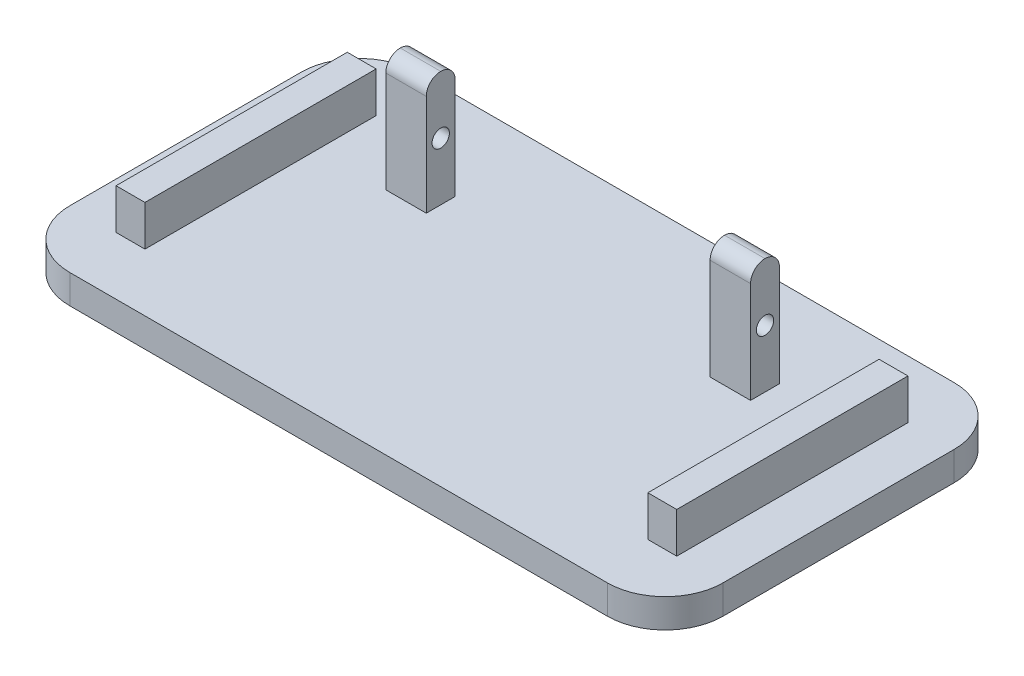
SolidWorks part; units mm, degrees
material "ABS"
ref_plane "Plano frontal" through (0, 0, 0) normal (0, 0, 1) x (1, 0, 0)
ref_plane "Plano superior" through (0, 0, 0) normal (0, 1, 0) x (1, 0, 0)
ref_plane "Plano direito" through (0, 0, 0) normal (1, 0, 0) x (0, 0, -1)
sketch "Esboço1" plane through (0, 0, 0) normal (0, 1, 0) x (1, 0, 0)
  line L1 (-13.2145, 15.5332) -> (79.7855, 15.5332)
  line L2 (-23.2145, 5.5332) -> (-23.2145, -34.4668)
  line L3 (-13.2145, -44.4668) -> (79.7855, -44.4668)
  line L4 (89.7855, 5.5332) -> (89.7855, -34.4668)
  arc A0 (89.7855, 5.5332) -> (79.7855, 15.5332) centre (79.7855, 5.5332) ccw
  arc A1 (89.7855, -34.4668) -> (79.7855, -44.4668) centre (79.7855, -34.4668) cw
  arc A2 (-13.2145, -44.4668) -> (-23.2145, -34.4668) centre (-13.2145, -34.4668) cw
  arc A3 (-23.2145, 5.5332) -> (-13.2145, 15.5332) centre (-13.2145, 5.5332) cw
  point P4 (33.2855, 15.5332)
  point P7 (89.7855, 15.5332)
  point P12 (-23.2145, -44.4668)
  point P15 (-23.2145, 15.5332)
  dimension "D4" = 10
  dimension "D1" = 113
  dimension "D2" = 56.5
  dimension "D3" = 60
extrude "Ressalto-extrusão1" add sketch "Esboço1" along normal blind 5
sketch "Esboço2" plane through (0, 5, 0) normal (0, 1, 0) x (1, 0, 0)
  line L0 (79.7855, 15.5332) -> (-13.2145, 15.5332) construction
  line L1 (-8.2645, -4.7476) -> (-8.2645, 0.2524) construction
  line L2 (64.3755, -4.7476) -> (64.3755, 0.2524) construction
  line L3 (-8.2645, -4.7476) -> (64.3755, -4.7476) construction
  line L4 (-8.2645, 0.2524) -> (64.3755, 0.2524) construction
  line L5 (57.8355, 0.2524) -> (57.8355, -4.7476)
  line L6 (1.7355, 0.2524) -> (8.7355, 0.2524)
  line L7 (1.7355, -4.7476) -> (8.7355, -4.7476)
  line L8 (1.7355, 0.2524) -> (1.7355, -4.7476)
  line L9 (8.7355, 0.2524) -> (8.7355, -4.7476)
  line L10 (64.8355, 0.2524) -> (64.8355, -4.7476)
  line L11 (57.8355, 0.2524) -> (64.8355, 0.2524)
  line L12 (57.8355, -4.7476) -> (64.8355, -4.7476)
  line L13 (89.7855, -34.4668) -> (89.7855, 5.5332) construction
  line L15 (-23.2145, 5.5332) -> (-23.2145, -34.4668) construction
  point P8 (1.7355, -2.2476)
  dimension "D1" = 49.1
  dimension "D2" = 7
  dimension "D3" = 24.95
  dimension "D4" = 24.95
  dimension "D5" = 7
  dimension "D6" = 15.2808
extrude "Ressalto-extrusão2" add sketch "Esboço2" along normal blind 20
sketch "Esboço4" plane through (1.7355, 0, 0) normal (-1, 0, 0) x (0, 0, 1)
  line L0 (-0.2524, 5) -> (4.7476, 5) construction
  line L1 (4.7476, 25) -> (4.7476, 5) construction
  circle A0 centre (2.2476, 15) radius 1.5
  dimension "D1" = 10
  dimension "D2" = 2.5
extrude "Corte-extrusão1" cut sketch "Esboço4" against normal through all
sketch "Esboço5" plane through (0, 5, 0) normal (0, 1, 0) x (1, 0, 0)
  line L0 (79.7855, 15.5332) -> (-13.2145, 15.5332) construction
  line L1 (-15.2145, 5.5332) -> (-10.2145, 5.5332)
  line L2 (-15.2145, 5.5332) -> (-15.2145, -34.4668)
  line L3 (-15.2145, -34.4668) -> (-10.2145, -34.4668)
  line L4 (-10.2145, 5.5332) -> (-10.2145, -34.4668)
  line L5 (-13.2145, -44.4668) -> (79.7855, -44.4668) construction
  line L6 (-23.2145, 5.5332) -> (-23.2145, -34.4668) construction
  line L7 (89.7855, -34.4668) -> (89.7855, 5.5332) construction
  line L8 (76.7855, 5.5332) -> (81.7855, 5.5332)
  line L9 (76.7855, 5.5332) -> (76.7855, -34.4668)
  line L10 (76.7855, -34.4668) -> (81.7855, -34.4668)
  line L11 (81.7855, 5.5332) -> (81.7855, -34.4668)
  dimension "D1" = 10
  dimension "D2" = 10
  dimension "D3" = 8
  dimension "D4" = 40
  dimension "D5" = 10
  dimension "D6" = 8
extrude "Ressalto-extrusão3" add sketch "Esboço5" along normal blind 7
fillet "Filete1" radius 2.5 1 edges at (5.2355, 25, -0.2524)
fillet "Filete2" radius 2.5 1 edges at (5.2355, 25, 4.7476)
fillet "Filete3" radius 2.5 2 edges at (61.3355, 25, 4.7476) (61.3355, 25, -0.2524)
